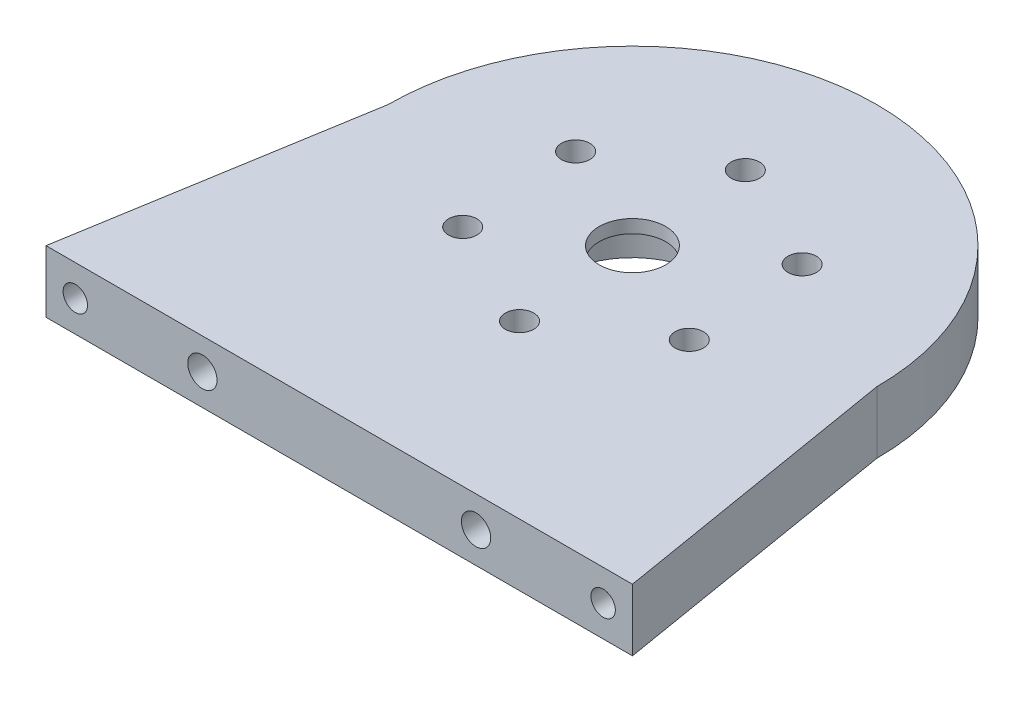
SolidWorks part; units mm, degrees
material "Aleación 6061"
ref_plane "Alzado" through (0, 0, 0) normal (0, 0, 1) x (1, 0, 0)
ref_plane "Planta" through (0, 0, 0) normal (0, 1, 0) x (1, 0, 0)
ref_plane "Vista lateral" through (0, 0, 0) normal (1, 0, 0) x (0, 0, -1)
ref_plane "Plano_xJ3" through (152.4, 0, 0) normal (1, 0, 0) x (0, 0, -1)
ref_plane "Plano_zJ5" through (0, 0, 336.55) normal (0, 0, 1) x (1, 0, 0)
ref_axis "Eje_J5" through (152.4, -30.8, 336.55) along (0, 1, 0)
ref_axis "Eje_J6" through (152.4, 0, 369.3) along (0, 0, -1)
sketch "Croquis8" plane through (0, 0, 0) normal (0, 1, 0) x (1, 0, 0)
  line L0 (127.4, -336.55) -> (177.4, -336.55)
  line L1 (177.4, -336.55) -> (182.4, -366.55)
  line L2 (182.4, -366.55) -> (122.4, -366.55)
  line L3 (122.4, -366.55) -> (127.4, -336.55)
  dimension "D1" = 127.4
  dimension "D2" = 336.55
  dimension "D3" = 177.4
  dimension "D4" = 336.55
  dimension "D5" = 182.4
  dimension "D6" = 366.55
  dimension "D7" = 122.4
  dimension "D8" = 366.55
extrude "Placa_J5" add sketch "Croquis8" along normal blind 6.35 from offset 3.175 offset against normal yes
sketch "Croquis9" plane through (0, 0, 0) normal (0, 1, 0) x (1, 0, 0)
  circle A0 centre (152.4, -336.55) radius 25
  dimension "D1" = 50
  dimension "D2" = 152.4
  dimension "D3" = 336.55
extrude "Placa_J5_redondeo" add sketch "Croquis9" along normal blind 6.35 from offset 3.175 offset against normal yes
sketch "Croquis10" plane through (0, 0, 0) normal (0, 1, 0) x (1, 0, 0)
  circle A0 centre (163.654, -341.9904) radius 1.45
  circle A1 centre (153.3155, -349.0164) radius 1.45
  circle A2 centre (142.0615, -343.576) radius 1.45
  circle A3 centre (141.146, -331.1096) radius 1.45
  circle A4 centre (151.4845, -324.0836) radius 1.45
  circle A5 centre (162.7385, -329.524) radius 1.45
  circle A6 centre (152.4, -336.55) radius 3.4
  dimension "D1" = 2.9
  dimension "D2" = 2.9
  dimension "D3" = 2.9
  dimension "D4" = 2.9
  dimension "D5" = 2.9
  dimension "D6" = 2.9
  dimension "D7" = 6.8
  dimension "D8" = 163.654
  dimension "D9" = 341.9904
  dimension "D10" = 153.3155
  dimension "D11" = 349.0164
  dimension "D12" = 142.0615
  dimension "D13" = 343.576
  dimension "D14" = 141.146
  dimension "D15" = 331.1096
  dimension "D16" = 151.4845
  dimension "D17" = 324.0836
  dimension "D18" = 162.7385
  dimension "D19" = 329.524
  dimension "D20" = 152.4
  dimension "D21" = 336.55
extrude "Barrenos_salida_M5" cut sketch "Croquis10" along normal blind 6.35 from offset 3.175 offset against normal yes
sketch "Croquis11" plane through (0, 0, 0) normal (0, 1, 0) x (1, 0, 0)
  circle A0 centre (163.654, -341.9904) radius 2.5
  circle A1 centre (153.3155, -349.0164) radius 2.5
  circle A2 centre (142.0615, -343.576) radius 2.5
  circle A3 centre (141.146, -331.1096) radius 2.5
  circle A4 centre (151.4845, -324.0836) radius 2.5
  circle A5 centre (162.7385, -329.524) radius 2.5
  dimension "D1" = 5
  dimension "D2" = 5
  dimension "D3" = 5
  dimension "D4" = 5
  dimension "D5" = 5
  dimension "D6" = 5
  dimension "D7" = 163.654
  dimension "D8" = 341.9904
  dimension "D9" = 153.3155
  dimension "D10" = 349.0164
  dimension "D11" = 142.0615
  dimension "D12" = 343.576
  dimension "D13" = 141.146
  dimension "D14" = 331.1096
  dimension "D15" = 151.4845
  dimension "D16" = 324.0836
  dimension "D17" = 162.7385
  dimension "D18" = 329.524
extrude "Refrentado_M2-5" cut sketch "Croquis11" along normal blind 2.6 from offset 3.175 offset against normal yes
sketch "Croquis12" plane through (0, 0, 0) normal (0, 0, 1) x (1, 0, 0)
  circle A0 centre (125.4, 0) radius 1.25
  circle A1 centre (179.4, 0) radius 1.25
  dimension "D1" = 2.5
  dimension "D2" = 2.5
  dimension "D3" = 125.4
  dimension "D4" = 179.4
extrude "Rosca_M3_canto" cut sketch "Croquis12" along normal blind 9 from offset 357.55
sketch "Croquis13" plane through (0, 0, 0) normal (0, 0, 1) x (1, 0, 0)
  circle A0 centre (138.4, 0) radius 1.5
  circle A1 centre (166.4, 0) radius 1.5
  dimension "D1" = 3
  dimension "D2" = 3
  dimension "D3" = 138.4
  dimension "D4" = 166.4
extrude "Pasadores_D3" cut sketch "Croquis13" along normal blind 7 from offset 359.55
sketch "Croquis14" plane through (0, -3.175, 0) normal (0, -1, 0) x (1, 0, 0)
  circle A0 centre (152.4, 336.55) radius 7.475
  dimension "D1" = 14.95
extrude "Cortar-Extruir1" cut sketch "Croquis14" against normal blind 5
